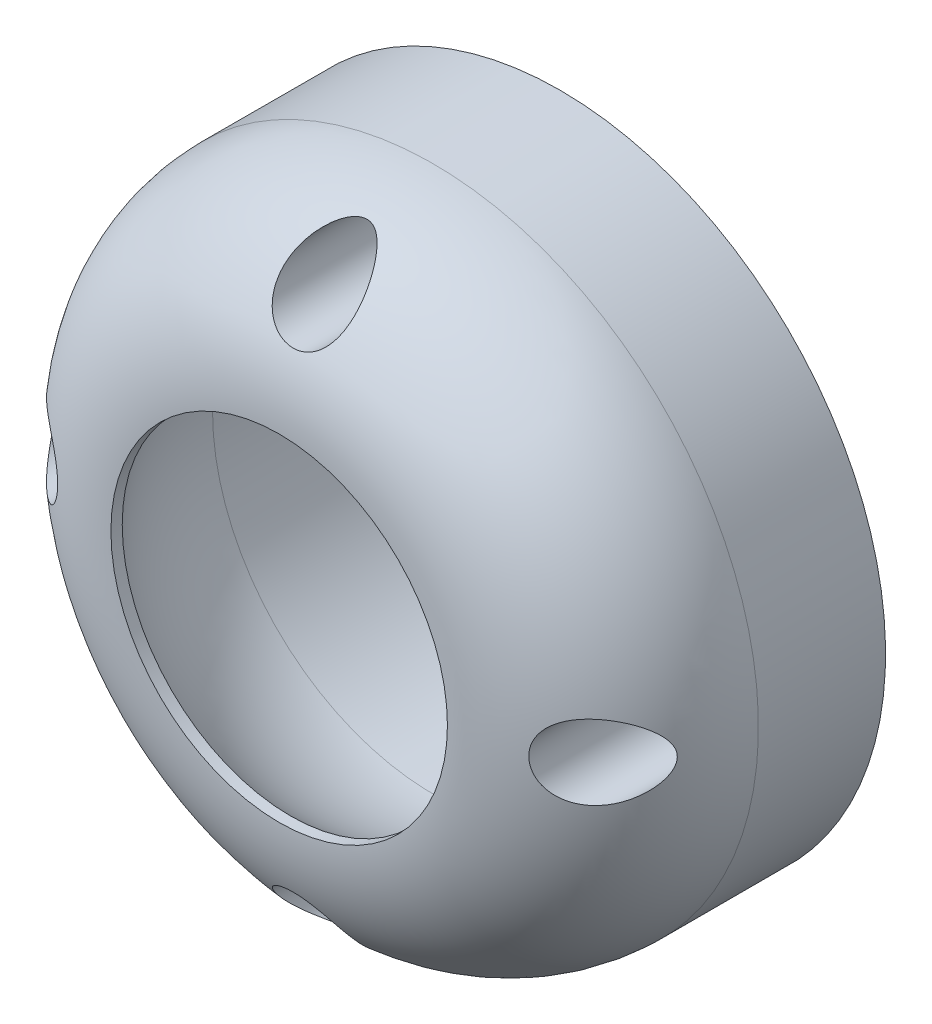
SolidWorks part; units mm, degrees
ref_plane "正面" through (0, 0, 0) normal (0, 0, 1) x (1, 0, 0)
ref_plane "平面" through (0, 0, 0) normal (0, 1, 0) x (1, 0, 0)
ref_plane "右側面" through (0, 0, 0) normal (1, 0, 0) x (0, 0, -1)
sketch "ｽｹｯﾁ1" plane through (0, 0, 0) normal (0, 0, 1) x (1, 0, 0)
  line L0 (-15.25, 0) -> (-14.75, 0)
  line L1 (14.75, 0) -> (15.25, 0)
  line L2 (14.75, 0) -> (-14.75, 0) construction
  arc A0 (14.75, 0) -> (-14.75, 0) centre (0, 0) cw
  arc A1 (-15.25, 0) -> (15.25, 0) centre (0, 0) ccw
  dimension "D2" = 14.75
  dimension "D1" = 15.25
revolve "回転1" add sketch "ｽｹｯﾁ1" angle 180 about L2
sketch "ｽｹｯﾁ2" plane through (0, 0, 0) normal (0, 0, -1) x (-1, 0, 0)
  circle A0 centre (0, 0) radius 11.25
  dimension "D1" = 22.5
extrude "ｶｯﾄ - 押し出し1" cut sketch "ｽｹｯﾁ2" against normal through all
sketch "ｽｹｯﾁ4" plane through (0, 0, 0) normal (1, 0, 0) x (0, 0, -1)
  line L0 (0, 15.25) -> (0, 21.75)
  line L1 (0, 0) -> (0, 15.25) construction
  line L2 (0, 0) -> (-17.7206, 0) construction
  arc A0 (-10.2956, 11.25) -> (0, 21.75) centre (0, 11.4524) cw
  arc A1 (0, 15.25) -> (-10.2956, 11.25) centre (0, 0) ccw
  arc A2 (0, 15.25) -> (-10.2956, 11.25) centre (0, 0) ccw construction
  dimension "D1" = 6.5
revolve "回転2" add sketch "ｽｹｯﾁ4" angle 360 about L2
sketch "ｽｹｯﾁ3" plane through (0, 0, 0) normal (0, 0, -1) x (-1, 0, 0)
  circle A0 centre (0, 0) radius 14.75
  circle A1 centre (0, 0) radius 21.75
  circle A2 centre (0, 0) radius 14.75 construction
  circle A4 centre (0, 0) radius 21.75 construction
  dimension "D1" = 7
extrude "ﾎﾞｽ - 押し出し1" add sketch "ｽｹｯﾁ3" along normal blind 8.5
sketch "ｽｹｯﾁ7" plane through (0, 0, -8.5) normal (0, 0, -1) x (-1, 0, 0)
  line L0 (0, -14.75) -> (0, 0) construction
  line L1 (0, -14.75) -> (0, -18.25) construction
  line L2 (0, -18.25) -> (0, -21.75) construction
  circle A0 centre (0, 0) radius 18.25 construction
  circle A3 centre (0, -18.25) radius 1.1
  circle A4 centre (-18.25, 0) radius 1.1
  circle A5 centre (0, 18.25) radius 1.1
  circle A6 centre (18.25, 0) radius 1.1
  circle A8 centre (0, 0) radius 21.75 construction
  circle A9 centre (0, 0) radius 14.75 construction
  point P23 (0, 0)
  dimension "D2" = 2.2
  dimension "D3" = 36.5
  dimension "D1" = 4
extrude "ｶｯﾄ - 押し出し2" cut sketch "ｽｹｯﾁ7" against normal through all
ref_plane "平面1" through (0, 0, 0) normal (0, 0, 1) x (1, 0, 0)
sketch "ｽｹｯﾁ8" plane through (0, 0, 0) normal (0, 0, 1) x (1, 0, 0)
  line L0 (0, 0) -> (0, 14.75) construction
  line L1 (0, 14.75) -> (0, 18.25) construction
  line L2 (0, 18.25) -> (0, 21.75) construction
  circle A0 centre (0, 0) radius 18.25 construction
  circle A2 centre (0, 18.25) radius 2.5
  circle A3 centre (0, 18.25) radius 1.1 construction
  circle A4 centre (18.25, 0) radius 2.5
  circle A5 centre (0, -18.25) radius 2.5
  circle A6 centre (-18.25, 0) radius 2.5
  circle A7 centre (0, 0) radius 21.75 construction
  point P21 (0, 0)
  point P24 (0, 0)
  dimension "D1" = 5
  dimension "D3" = 3.5
  dimension "D2" = 4
extrude "ｶｯﾄ - 押し出し7" cut sketch "ｽｹｯﾁ8" along normal through all from offset 6.5 offset against normal yes
